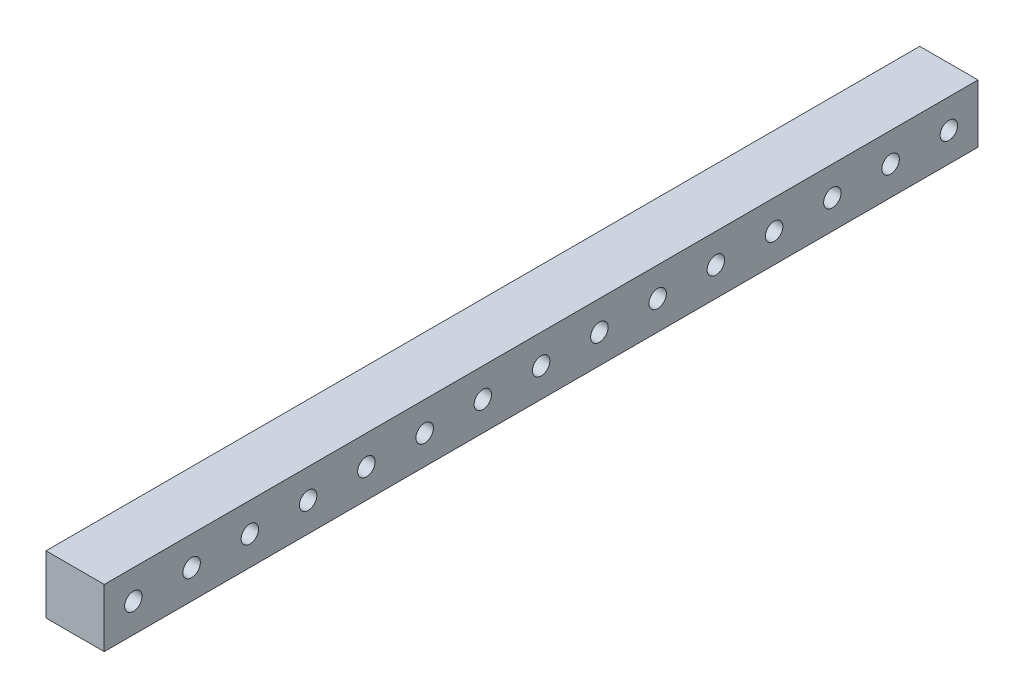
SolidWorks part; units mm, degrees
ref_plane "Front Plane" through (0, 0, 0) normal (0, 0, 1) x (1, 0, 0)
ref_plane "Top Plane" through (0, 0, 0) normal (0, 1, 0) x (1, 0, 0)
ref_plane "Right Plane" through (0, 0, 0) normal (1, 0, 0) x (0, 0, -1)
sketch "Sketch1" plane through (0, 0, 0) normal (0, 0, 1) x (1, 0, 0)
  line L0 (-10, -10) -> (10, 10) construction
  line L1 (-10, 10) -> (10, 10)
  line L2 (-10, 10) -> (-10, -10)
  line L3 (-10, -10) -> (10, -10)
  line L4 (10, 10) -> (10, -10)
  point P4 (0, 0)
  dimension "D1" = 20
  dimension "D2" = 45
extrude "Boss-Extrude1" add sketch "Sketch1" along normal blind 300
hole_wizard "Ø6.0mm Dowel Hole1" positions "Sketch2" profile "Sketch3" hole size "Ø6.0" standard "ANSI Metric" end condition through all
sketch "Sketch2" plane through (10, 0, 0) normal (1, 0, 0) x (0, 0, -1)
  line L0 (0, -10) -> (0, 10) construction
  point P0 (-10, 0)
  point P7 (0, 0)
  dimension "D1" = 10
sketch "Sketch3" plane through (10, 0, 10) normal (0, 1, 0) x (0, 0, -1)
  line L0 (0, 0) -> (0, 20)
  line L1 (0, 20) -> (3, 20)
  line L2 (3, 20) -> (3, 0)
  line L5 (3, 0) -> (0, 0)
  line L11 (0, -6.35) -> (0, 107.95) construction
  dimension "Thru Hole Dia." = 6
  dimension "Thru Hole Depth" = 20
pattern_linear "LPattern2" count 15 spacing 20 along (0, 0, 1) of "Ø6.0mm Dowel Hole1"
